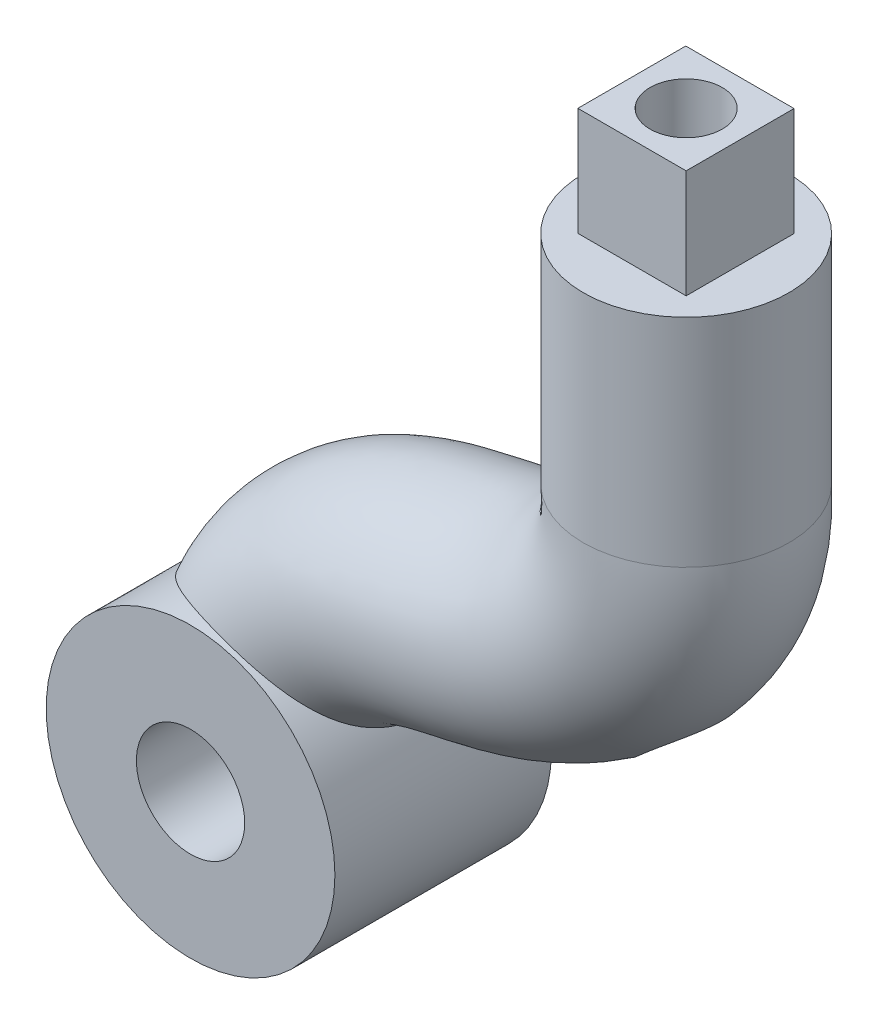
SolidWorks part; units mm, degrees
ref_plane "Ebene vorne" through (0, 0, 0) normal (0, 0, 1) x (1, 0, 0)
ref_plane "Ebene oben" through (0, 0, 0) normal (0, 1, 0) x (1, 0, 0)
ref_plane "Ebene rechts" through (0, 0, 0) normal (1, 0, 0) x (0, 0, -1)
sketch "Skizze2" plane through (0, 0, 0) normal (0, 0, 1) x (1, 0, 0)
  circle A0 centre (0, 0) radius 4
  circle A1 centre (0, 0) radius 1.5
extrude "Aufsatz-Linear austragen1" add sketch "Skizze2" along normal blind 6
ref_plane "Ebene2" through (0, 0, 3) normal (0, 0, 1) x (1, 0, 0)
sketch "Skizze5" plane through (0, 0, 3) normal (0, 0, 1) x (1, 0, 0)
  spline S0 degree 3 poles (0, 0) (-0.501, 1.9156) (1.8273, 5.453) (7.6595, 5.7189) (10.9406, 8.6532) (10.7311, 11.2633) knots 0 0 0 0 0.336029 0.590083 1 1 1 1
ref_plane "Ebene3" through (0, 11.2633, 0) normal (0, 1, 0) x (1, 0, 0)
sketch "Skizze6" plane through (0, 11.2633, 0) normal (0, 1, 0) x (1, 0, 0)
  circle A0 centre (10.7311, -3) radius 2.85
  dimension "D1" = 5.7
sweep "Austragung2" add profiles "Skizze6" path "Skizze5"
sketch "Skizze7" plane through (0, 0, 6) normal (0, 0, 1) x (1, 0, 0)
  circle A0 centre (0, 0) radius 1.5
extrude "Schnitt-Linear austragen1" cut sketch "Skizze7" against normal blind 6
sketch "Skizze9" plane through (0, 11.2633, 0) normal (0, 1, 0) x (1, 0, 0)
  circle A0 centre (10.7311, -3) radius 2.85
  dimension "D1" = 5.7
extrude "Aufsatz-Linear austragen4" add sketch "Skizze9" along normal blind 6
sketch "Skizze10" plane through (0, 17.2633, 0) normal (0, 1, 0) x (1, 0, 0)
  line L0 (10.7311, -3) -> (14.8017, -3) construction
  line L1 (14.8017, -3) -> (7.0685, -3) construction
  line L2 (10.7311, -3) -> (10.7311, -7.7395) construction
  line L3 (10.7311, -3) -> (10.7311, 2.5867) construction
  line L4 (9.2311, -4.5) -> (12.2311, -4.5)
  line L5 (10.7311, -1.5101) -> (9.2311, -1.5101)
  line L6 (9.2311, -1.5101) -> (9.2311, -4.5)
  line L7 (12.2311, -4.5) -> (12.2311, -1.5101)
  line L8 (12.2311, -1.5101) -> (10.7311, -1.5101)
  circle A0 centre (10.7311, -3) radius 2.85 construction
  dimension "D1" = 1.5
  dimension "D2" = 1.5
extrude "Aufsatz-Linear austragen5" add sketch "Skizze10" along normal blind 3
sketch "Skizze12" plane through (0, 20.2633, 0) normal (0, 1, 0) x (1, 0, 0)
  line L0 (9.2311, -4.5) -> (12.2311, -4.5) construction
  line L1 (12.2311, -4.5) -> (12.2311, -1.5101) construction
  circle A0 centre (10.7311, -3) radius 1
  dimension "D1" = 1.5
  dimension "D2" = 1.5
extrude "Schnitt-Linear austragen2" cut sketch "Skizze12" against normal blind 20
